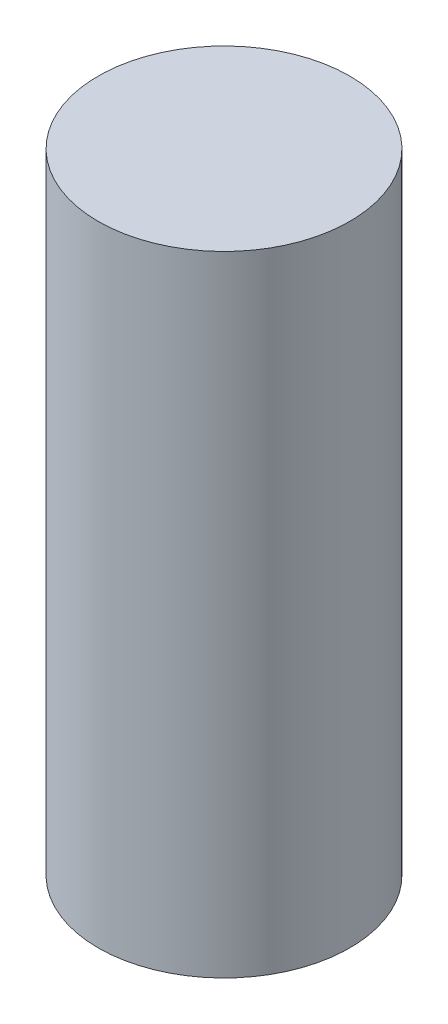
SolidWorks part; units mm, degrees
ref_plane "前视基准面" through (0, 0, 0) normal (0, 0, 1) x (1, 0, 0)
ref_plane "上视基准面" through (0, 0, 0) normal (0, 1, 0) x (1, 0, 0)
ref_plane "右视基准面" through (0, 0, 0) normal (1, 0, 0) x (0, 0, -1)
other "Configuration Table"
sketch "草图1" plane through (0, 0, 0) normal (0, 1, 0) x (1, 0, 0)
  circle A0 centre (0, 0) radius 300
  dimension "D1" = 600
extrude "凸台-拉伸1" add sketch "草图1" along normal blind 1500
ref_axis "基准轴1" through (0, 1500, 0) along (0, -1, 0)
